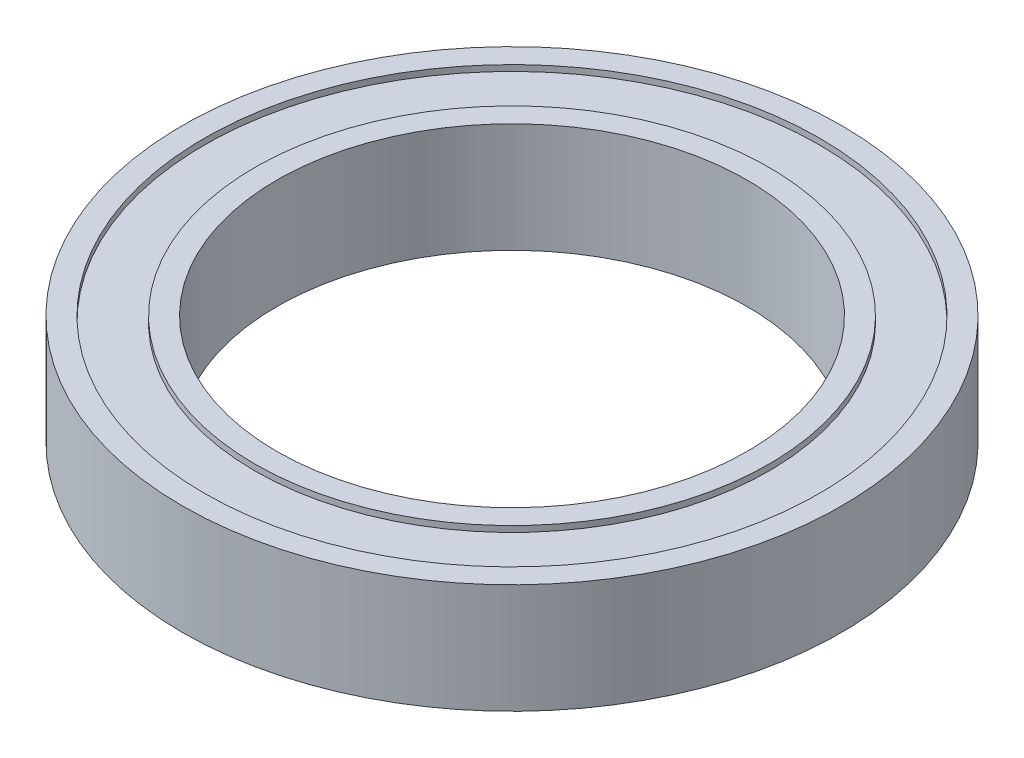
SolidWorks part; units mm, degrees
ref_plane "Front Plane" through (0, 0, 0) normal (0, 0, 1) x (1, 0, 0)
ref_plane "Top Plane" through (0, 0, 0) normal (0, 1, 0) x (1, 0, 0)
ref_plane "Right Plane" through (0, 0, 0) normal (1, 0, 0) x (0, 0, -1)
sketch "Sketch1" plane through (0, 0, 0) normal (0, 1, 0) x (1, 0, 0)
  circle A0 centre (0, 0) radius 21.0058
  circle A1 centre (0, 0) radius 14.986
  circle A2 centre (0, 0) radius 16.383
  circle A3 centre (0, 0) radius 19.6088
  dimension "D1" = 29.972
  dimension "D2" = 42.0116
  dimension "D3" = 1.397
  dimension "D4" = 1.397
extrude "Boss-Extrude1" add sketch "Sketch1" along normal blind 3.4925 and the other way blind 3.4925 contours A2 A1 | A0 A3 region at (-20.4117, 0, 0) region at (-15.9196, 0, 0)
extrude "Boss-Extrude2" add sketch "Sketch1<3>" along normal blind 3.1115 and the other way blind 3.1115 contours A3 A2 region at (-19.0542, 0, 0)
sketch "Sketch1<3>" plane through (0, 0, 0) normal (0, 1, 0) x (1, 0, 0) same geometry as "Sketch1"
